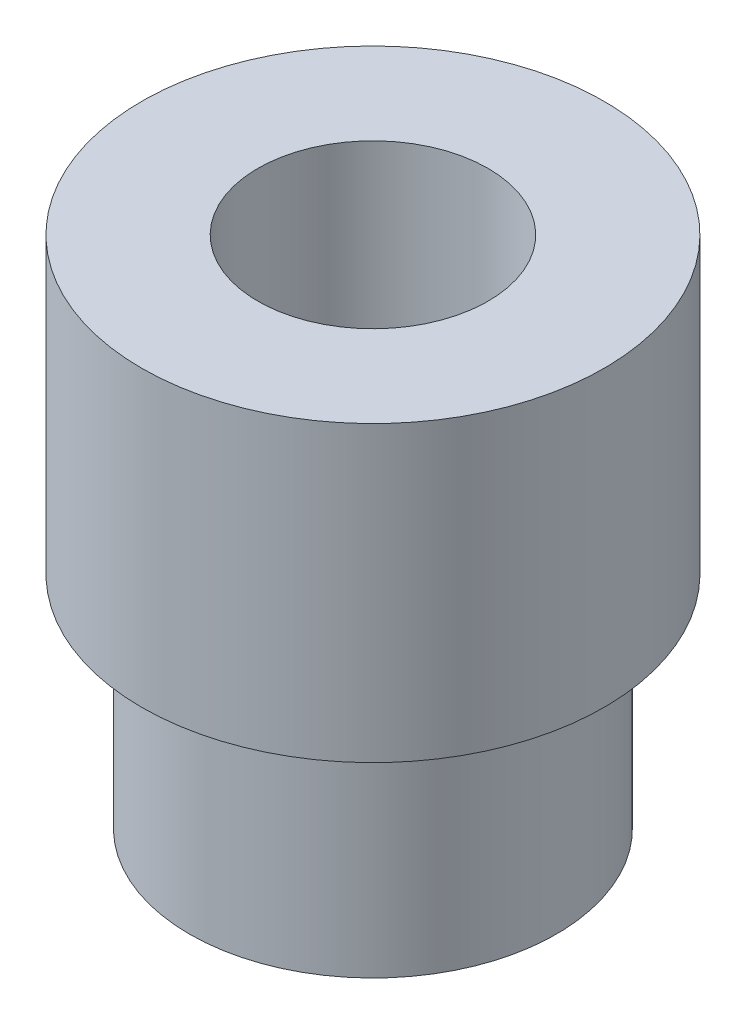
SolidWorks part; units mm, degrees
material "6061 Alloy"
ref_plane "Front Plane" through (0, 0, 0) normal (0, 0, 1) x (1, 0, 0)
ref_plane "Top Plane" through (0, 0, 0) normal (0, 1, 0) x (1, 0, 0)
ref_plane "Right Plane" through (0, 0, 0) normal (1, 0, 0) x (0, 0, -1)
sketch "Sketch1" plane through (0, 0, 0) normal (0, 1, 0) x (1, 0, 0)
  circle A0 centre (0, 0) radius 3.9688
  circle A1 centre (0, 0) radius 5
  dimension "D1" = 10
  dimension "D2" = 7.9375
extrude "Bearing Collar" add sketch "Sketch1" along normal blind 6.35 contours A0 | A1 A0 region at (0, 0, 0) region at (-4.8586, 0, 0)
extrude "Center Spindle" add sketch "Sketch1<3>" against normal blind 4.7625 contours A0 region at (0, 0, 0)
sketch "Sketch1<3>" plane through (0, 0, 0) normal (0, 1, 0) x (1, 0, 0) same geometry as "Sketch1"
hole_wizard "#10 Clearance Hole1" positions "3DSketch1" profile "Sketch2" hole size "#10" standard "ANSI Inch" end condition through all
sketch3d "3DSketch1"
  line L0 (0, -4.7625, 0) -> (0, 0, 0) construction
  circle A0 centre (0, -4.7625, 0) radius 3.9688
  circle A1 centre (0, -4.7625, 0) radius 3.9688 construction
  point P0 (0, -4.7625, 0)
  point P5 (0, -0.7938, 0)
  point P15 (0, -0.7938, 0)
sketch "Sketch2" plane through (0, -4.7625, 0) normal (1, 0, 0) x (0, 0, -1)
  line L0 (0, 0) -> (0, 11.1125)
  line L1 (0, 11.1125) -> (2.4892, 11.1125)
  line L2 (2.4892, 11.1125) -> (2.4892, 0)
  line L5 (2.4892, 0) -> (0, 0)
  line L11 (0, -6.35) -> (0, 107.95) construction
  dimension "Thru Hole Dia." = 4.9784
  dimension "Thru Hole Depth" = 11.1125
